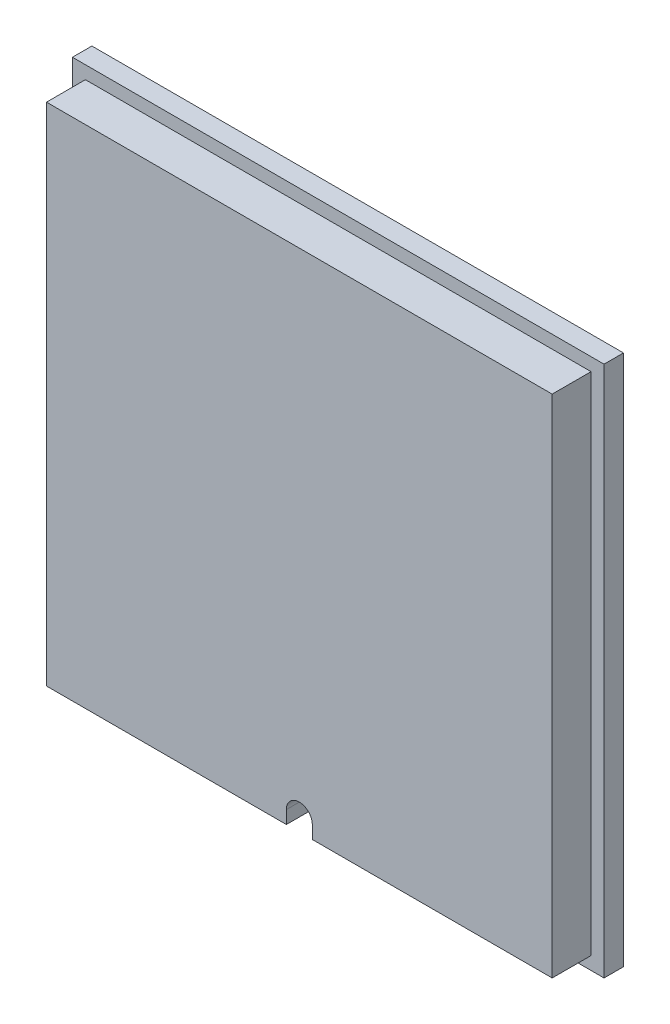
SolidWorks part; units mm, degrees
material "Maple"
ref_plane "Front Plane" through (0, 0, 0) normal (0, 0, 1) x (1, 0, 0)
ref_plane "Top Plane" through (0, 0, 0) normal (0, 1, 0) x (1, 0, 0)
ref_plane "Right Plane" through (0, 0, 0) normal (1, 0, 0) x (0, 0, -1)
sketch "Sketch1" plane through (0, 0, 0) normal (0, 0, 1) x (1, 0, 0)
  line L1 (-39, -39) -> (39, -39)
  line L2 (-39, -39) -> (-39, 39)
  line L3 (-39, 39) -> (39, 39)
  line L4 (39, -39) -> (39, 39)
  line L5 (-39, -39) -> (39, 39) construction
  line L6 (-39, 39) -> (39, -39) construction
  point P0 (0, 0)
  dimension "D1" = 78
  dimension "D2" = 78
extrude "Boss-Extrude1" add sketch "Sketch1" along normal blind 9
sketch "Sketch2" plane through (0, 0, 0) normal (0, 0, 1) x (1, 0, 0)
  line L8 (41, -41) -> (41, 41)
  line L9 (-41, -41) -> (41, -41)
  line L10 (-41, 41) -> (-41, -41)
  line L11 (41, 41) -> (-41, 41)
  line L12 (41, -41) -> (41, 41)
  line L13 (-41, -41) -> (41, -41)
  line L14 (-41, 41) -> (-41, -41)
  line L15 (41, 41) -> (-41, 41)
  dimension "D1" = 2
extrude "Boss-Extrude2" add sketch "Sketch2" along normal blind 3
sketch "Sketch3" plane through (0, 0, 9) normal (0, 0, 1) x (1, 0, 0)
  line L0 (-39, -39) -> (39, -39) construction
  line L1 (0, -37) -> (0, -41) construction
  line L2 (2, -37) -> (2, -41)
  line L3 (-2, -37) -> (-2, -41)
  line L4 (-41, -41) -> (41, -41) construction
  arc A1 (2, -37) -> (-2, -37) centre (0, -37) ccw
  arc A2 (-2, -41) -> (2, -41) centre (0, -41) ccw
  point P4 (0, -39)
  dimension "D1" = 4
  dimension "D2" = 2
extrude "Cut-Extrude1" cut sketch "Sketch3" against normal through all
